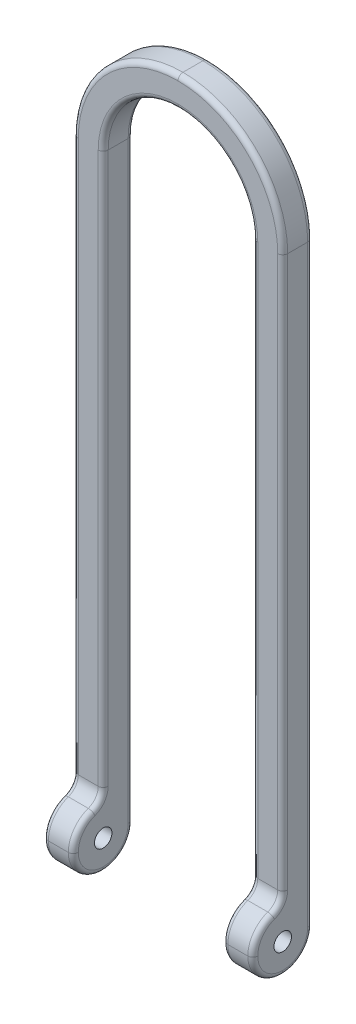
SolidWorks part; units mm, degrees
ref_plane "Plan de face" through (0, 0, 0) normal (0, 0, 1) x (1, 0, 0)
ref_plane "Plan de dessus" through (0, 0, 0) normal (0, 1, 0) x (1, 0, 0)
ref_plane "Plan de droite" through (0, 0, 0) normal (1, 0, 0) x (0, 0, -1)
sketch "Esquisse1" plane through (0, 0, 0) normal (0, 0, 1) x (1, 0, 0)
  line L0 (0, 0) -> (0, 140) construction
  line L1 (15, 0) -> (15, 140)
  line L2 (15, 140) -> (-15, 140)
  line L3 (15, 0) -> (21, 0)
  line L4 (21, 0) -> (21, 146)
  line L5 (21, 146) -> (-21, 146)
  line L6 (-21, 0) -> (-21, 146)
  line L7 (-15, 0) -> (-21, 0)
  line L8 (-15, 0) -> (-15, 140)
  point P10 (0, 146)
  dimension "D1" = 6
  dimension "D2" = 6
  dimension "D3" = 140
  dimension "D4" = 30
extrude "Boss.-Extru.1" add sketch "Esquisse1" along normal blind 6
sketch "Esquisse2" plane through (21, 0, 0) normal (1, 0, 0) x (0, 0, -1)
  line L0 (-6, 0) -> (-6, 146) construction
  line L1 (-6, 0) -> (-12, 0)
  line L2 (-6, 0) -> (-6, 12)
  line L3 (-6, 12) -> (-12, 12)
  line L4 (-12, 0) -> (-12, 12)
  line L5 (-6, 0) -> (0, 0) construction
  dimension "D1" = 6
  dimension "D2" = 12
extrude "Boss.-Extru.2" add sketch "Esquisse2" against normal up to vertex (6 mm away) up to point (15, 0, 6)
extrude "Boss.-Extru.3" add sketch "Esquisse2<2>" against normal blind 6 from vertex starting at point (-15, 0, 6)
sketch "Esquisse2<2>" plane through (21, 0, 0) normal (1, 0, 0) x (0, 0, -1) same geometry as "Esquisse2"
fillet "Congé1" radius 15 2 edges at (15, 140, 3) (-15, 140, 3)
fillet "Congé2" radius 21 2 edges at (21, 146, 3) (-21, 146, 3)
sketch "Esquisse3" plane through (-21, 0, 0) normal (-1, 0, 0) x (0, 0, 1)
  line L0 (12, 6) -> (6, 6) construction
  line L1 (12, 12) -> (12, 0) construction
  circle A0 centre (6, 6) radius 1.75
  dimension "D1" = 3.5
  dimension "D2" = 6
extrude "Enlèv. mat.-Extru.1" cut sketch "Esquisse3" against normal through all both and the other way through all
fillet "Congé4" radius 6 6 edges at (18, 0, 0) (-18, 0, 0) (18, 0, 12) (-18, 0, 12) (18, 12, 12) (-18, 12, 12)
fillet "Congé5" radius 3 2 edges at (18, 12, 6) (-18, 12, 6)
fillet "Congé6" radius 1 32 edges at (21, 12.7532, 6.5505) (21, 9.4641, 10.899) (21, 1.7574, 10.2426) (21, 1.7574, 1.7574) (21, 65.5, 0) (14.8492, 139.8492, 0) (-14.8492, 139.8492, 0) (-21, 65.5, 0) (-21, 1.7574, 1.7574) (-21, 1.7574, 10.2426) (-21, 9.4641, 10.899) (-21, 12.7532, 6.5505) (-15, 12.7532, 6.5505) (-15, 9.4641, 10.899) (-15, 1.7574, 10.2426) (-15, 1.7574, 1.7574) (-15, 65.5, 0) (-10.6066, 135.6066, 0) (10.6066, 135.6066, 0) (15, 65.5, 0) (15, 1.7574, 1.7574) (15, 1.7574, 10.2426) (15, 9.4641, 10.899) (15, 12.7532, 6.5505) (10.6066, 135.6066, 6) (-10.6066, 135.6066, 6) (-15, 69.7426, 6) (-21, 69.7426, 6) (-14.8492, 139.8492, 6) (14.8492, 139.8492, 6) (21, 69.7426, 6) (15, 69.7426, 6)
